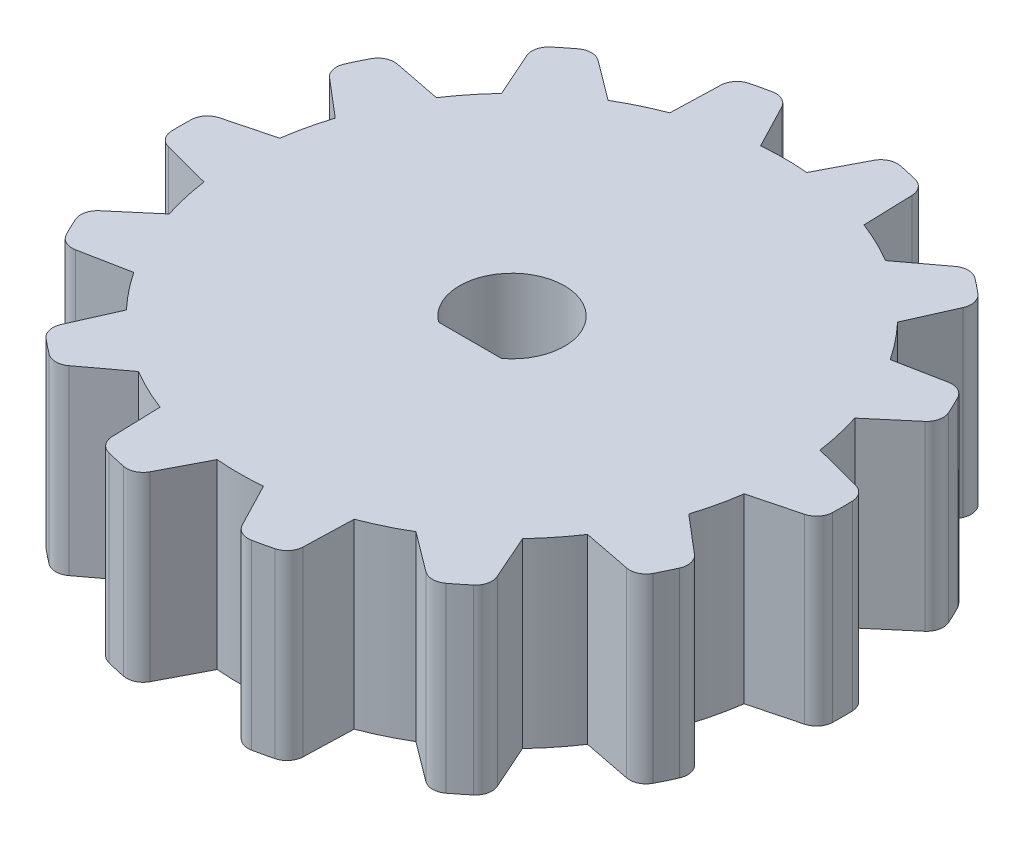
SolidWorks part; units mm, degrees
ref_plane "Front Plane" through (0, 0, 0) normal (0, 0, 1) x (1, 0, 0)
ref_plane "Top Plane" through (0, 0, 0) normal (0, 1, 0) x (1, 0, 0)
ref_plane "Right Plane" through (0, 0, 0) normal (1, 0, 0) x (0, 0, -1)
sketch "Sketch1" plane through (0, 0, 0) normal (0, 1, 0) x (1, 0, 0)
  circle A0 centre (0, 0) radius 20
  dimension "D1" = 40
extrude "Boss-Extrude1" add sketch "Sketch1" along normal blind 11
sketch "Sketch2" plane through (0, 11, 0) normal (0, 1, 0) x (1, 0, 0)
  line L0 (-3.125, 19.7544) -> (-1.3999, 16.4405)
  line L2 (1.3999, 16.4405) -> (3.125, 19.7544)
  circle A0 centre (0, 0) radius 20 construction
  arc A1 (-1.3999, 16.4405) -> (1.3999, 16.4405) centre (0, 0) cw
  arc A2 (3.125, 19.7544) -> (-3.125, 19.7544) centre (0, 0) ccw
  point P6 (0, 16.5)
  dimension "D1" = 16.5
  dimension "D2" = 55
  dimension "D3" = 6.25
extrude "Cut-Extrude1" cut sketch "Sketch2" against normal up to next
fillet "Fillet1" radius 1 2 edges at (3.125, 5.5, -19.7544) (-3.125, 5.5, -19.7544)
pattern_circular "CirPattern1" count 14 over 360 about axis through (0, 11, 0) along (0, -1, 0) of "Cut-Extrude1", "Fillet1"
sketch "Sketch3" plane through (0, 11, 0) normal (0, 1, 0) x (1, 0, 0)
  line L0 (1.905, -2.54) -> (-1.905, -2.54)
  arc A0 (1.905, -2.54) -> (-1.905, -2.54) centre (0, 0) ccw
  point P1 (0, 3.175)
  dimension "D1" = 3.175
  dimension "D2" = 5.715
extrude "Cut-Extrude2" cut sketch "Sketch3" against normal up to next
